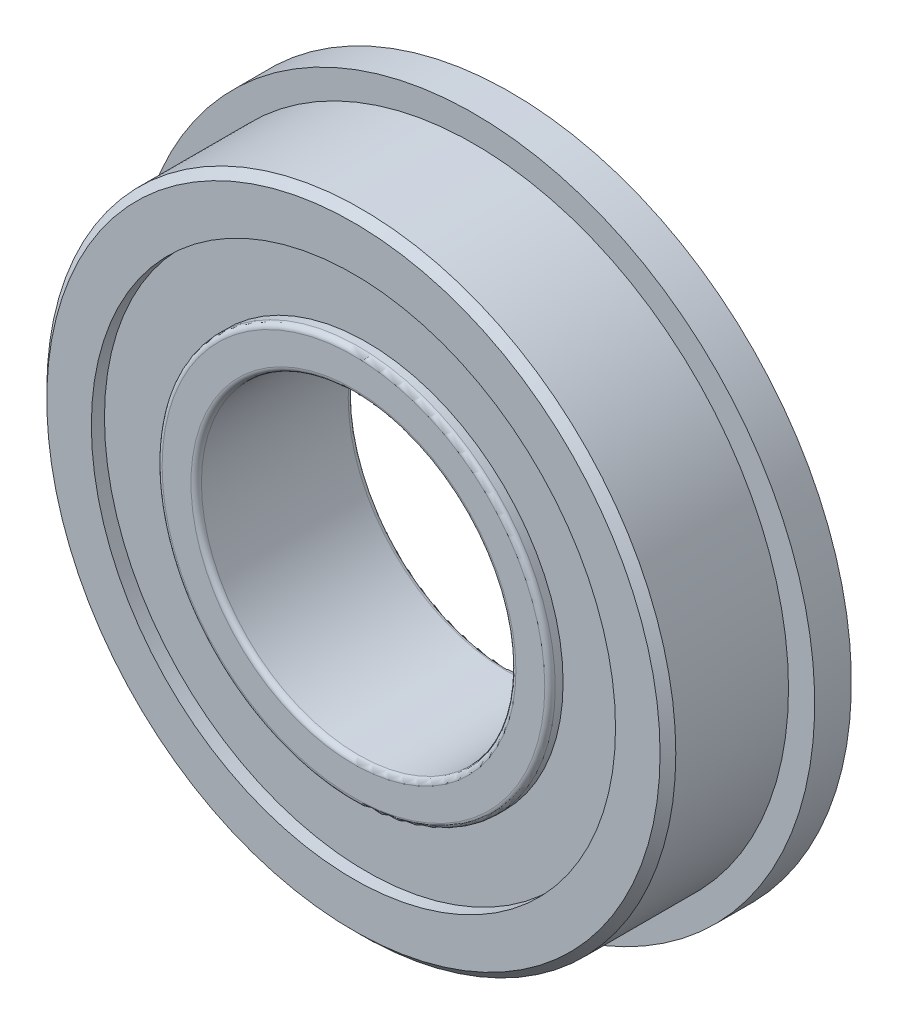
SolidWorks part; units mm, degrees
ref_plane "正面" through (0, 0, 0) normal (0, 0, 1) x (1, 0, 0)
ref_plane "平面" through (0, 0, 0) normal (0, 1, 0) x (1, 0, 0)
ref_plane "右側面" through (0, 0, 0) normal (1, 0, 0) x (0, 0, -1)
sketch "Sketch1" plane through (0, 0, 0) normal (0, 0, 1) x (1, 0, 0)
  circle A0 centre (0, 0) radius 12
  circle A1 centre (0, 0) radius 6
  dimension "D1" = 24
  dimension "D2" = 12
extrude "Boss-Extrude1" add sketch "Sketch1" along normal blind 4.6
sketch "Sketch2" plane through (0, 0, 0) normal (0, 0, -1) x (-1, 0, 0)
  circle A0 centre (0, 0) radius 13
  circle A1 centre (0, 0) radius 6
  dimension "D1" = 12
  dimension "D2" = 26
extrude "Boss-Extrude2" add sketch "Sketch2" along normal blind 1.4
sketch "Sketch4" plane through (0, 0, 4.6) normal (0, 0, 1) x (1, 0, 0)
  circle A0 centre (0, 0) radius 7.5
  circle A1 centre (0, 0) radius 10
  dimension "D1" = 15
  dimension "D2" = 20
extrude "Cut-Extrude1" cut sketch "Sketch4" against normal blind 0.5
chamfer "Chamfer1" distance 0.3 angle 45 1 edges at (12, 0, 4.6)
sketch "Sketch5" plane through (0, 0, -1.4) normal (0, 0, -1) x (-1, 0, 0)
  circle A0 centre (0, 0) radius 7.5
  circle A1 centre (0, 0) radius 10
  dimension "D1" = 15
  dimension "D2" = 20
extrude "Cut-Extrude2" cut sketch "Sketch5" against normal blind 0.2
fillet "Fillet1" radius 0.2 4 edges at (7.5, 0, 4.6) (6, 0, 4.6) (-7.5, 0, -1.4) (-6, 0, -1.4)
